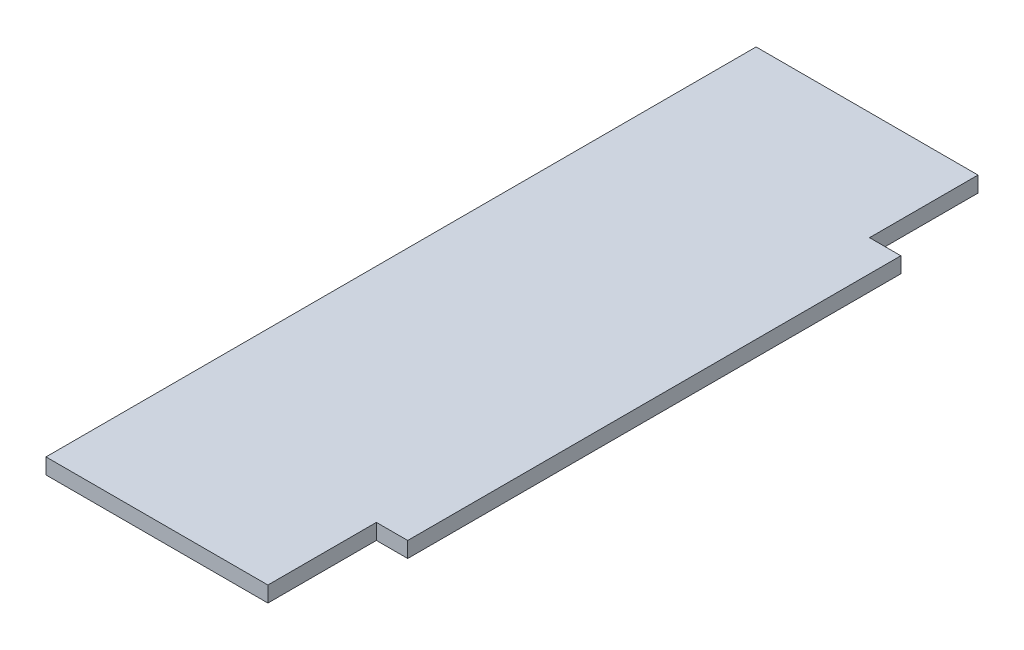
SolidWorks part; units mm, degrees
ref_plane "Front Plane" through (0, 0, 0) normal (0, 0, 1) x (1, 0, 0)
ref_plane "Top Plane" through (0, 0, 0) normal (0, 1, 0) x (1, 0, 0)
ref_plane "Right Plane" through (0, 0, 0) normal (1, 0, 0) x (0, 0, -1)
sketch "Sketch1" plane through (0, 0, 0) normal (0, 1, 0) x (1, 0, 0)
  line L0 (-22.5, 22) -> (22.5, 22)
  line L1 (22.5, 22) -> (22.5, 0)
  line L2 (22.5, 0) -> (28.85, 0)
  line L3 (28.85, 0) -> (28.85, -100)
  line L4 (28.85, -100) -> (22.5, -100)
  line L5 (22.5, -100) -> (22.5, -122)
  line L6 (22.5, -122) -> (-22.5, -122)
  line L7 (-22.5, -122) -> (-22.5, -100)
  line L8 (-22.5, -100) -> (-28.85, -100)
  line L9 (-28.85, -100) -> (-28.85, 0)
  line L10 (-28.85, 0) -> (-22.5, 0)
  line L11 (-22.5, 0) -> (-22.5, 22)
  line L12 (-22.5, 0) -> (-22.5, -100) construction
  point P11 (0, 22)
  point P14 (-28.85, -50)
  dimension "D1" = 6.35
  dimension "D2" = 100
  dimension "D3" = 45
  dimension "D4" = 144
extrude "Boss-Extrude1" add sketch "Sketch1" along normal blind 3.175 contours L11 L12 L7 L6 L5 L4 L3 L2 L1 L0 region at (2.2914, 0, 50)
equation "\"length\" = 144mm"
equation "\"w_mach\"= 45mm"
equation "\"w_tab\"= 100mm"
equation "\"t_wood\"= 0.125in"
equation "\"t_side\"= 0.25in"
equation "\"D1@Sketch1\"=\"t_side\""
equation "\"D2@Sketch1\"=\"w_tab\""
equation "\"D3@Sketch1\"=\"w_mach\""
equation "\"D4@Sketch1\"=\"length\""
equation "\"D1@Boss-Extrude1\"=\"t_wood\""
